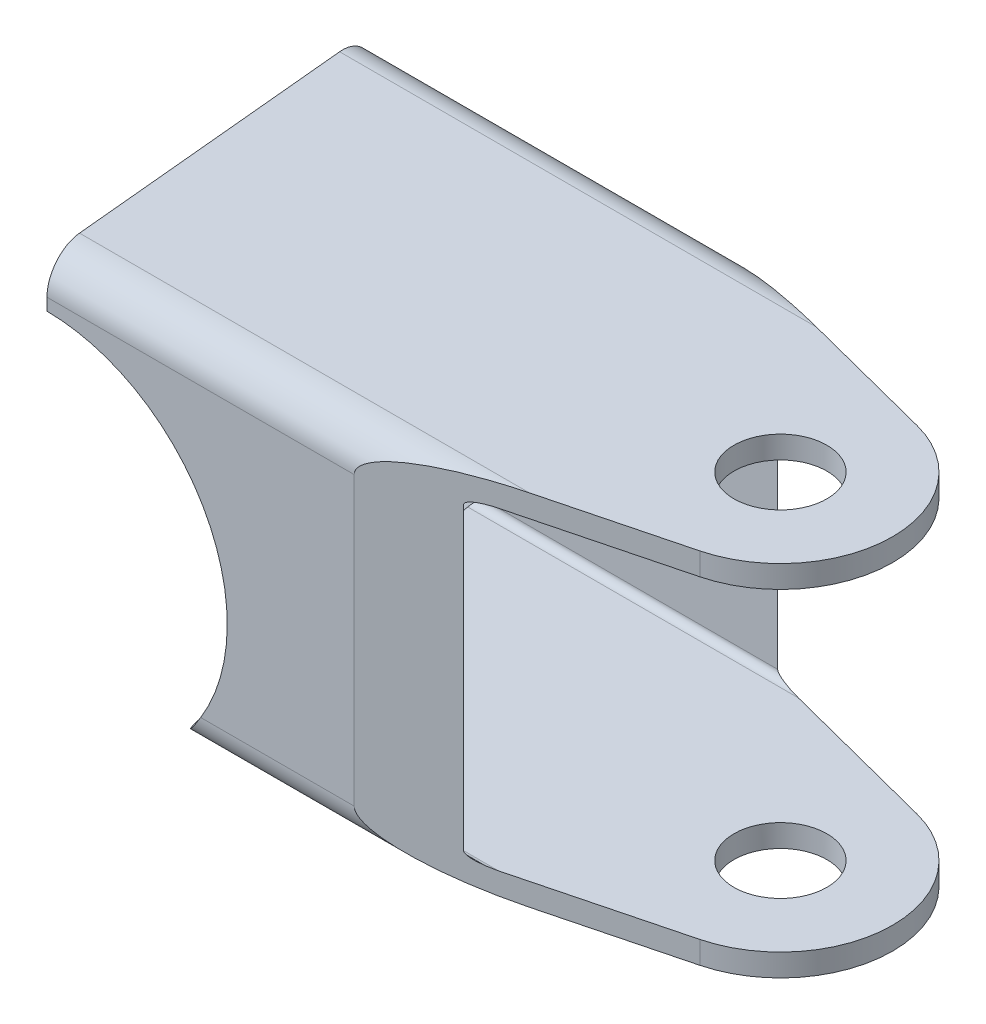
SolidWorks part; units mm, degrees
note: '?' marks a value the reader was unsure of.
material "AISI 4130 Steel, annealed at 865C"
ref_plane "Front Plane" through (0, 0, 0) normal (0, 0, 1) x (1, 0, 0)
ref_plane "Top Plane" through (0, 0, 0) normal (0, 1, 0) x (1, 0, 0)
ref_plane "Right Plane" through (0, 0, 0) normal (1, 0, 0) x (0, 0, -1)
sketch "Sketch1" plane through (0, 0, 0) normal (1, 0, 0) x (0, 0, -1)
  line L1 (-10.16, 12.7) -> (10.16, 12.7)
  line L2 (-12.7, 10.16) -> (-12.7, -10.16)
  line L3 (-10.16, -12.7) -> (10.16, -12.7)
  line L4 (12.7, 10.16) -> (12.7, -10.16)
  arc A0 (-10.16, 12.7) -> (-12.7, 10.16) centre (-10.16, 10.16) ccw
  arc A1 (-10.16, -12.7) -> (-12.7, -10.16) centre (-10.16, -10.16) cw
  arc A2 (10.16, 12.7) -> (12.7, 10.16) centre (10.16, 10.16) cw
  arc A3 (12.7, -10.16) -> (10.16, -12.7) centre (10.16, -10.16) cw
  point P4 (0, -12.7)
  point P7 (0, 0)
  point P15 (12.7, 0)
  dimension "D3" = 2.54
  dimension "D4" = 2.54
  dimension "D5" = 2.54
  dimension "D6" = 2.54
  dimension "D1" = 25.4
  dimension "D2" = 20.32
extrude "Boss-Extrude1" add sketch "Sketch1" along normal blind 25.4 and the other way blind 34.925
sketch "Sketch11" plane through (25.4, 0, 0) normal (1, 0, 0) x (0, 0, -1)
  line L0 (-10.16, -12.7) -> (10.16, -12.7) construction
  line L1 (-10.6045, 11.1125) -> (10.6045, 11.1125)
  line L2 (-11.1125, 10.6045) -> (-11.1125, -10.6045)
  line L3 (-10.6045, -11.1125) -> (10.6045, -11.1125)
  line L4 (11.1125, 10.6045) -> (11.1125, -10.6045)
  line L5 (10.16, 12.7) -> (-10.16, 12.7) construction
  line L6 (12.7, -10.16) -> (12.7, 10.16) construction
  line L7 (-12.7, 10.16) -> (-12.7, -10.16) construction
  arc A0 (10.6045, 11.1125) -> (11.1125, 10.6045) centre (10.6045, 10.6045) cw
  arc A1 (10.6045, -11.1125) -> (11.1125, -10.6045) centre (10.6045, -10.6045) ccw
  arc A2 (-11.1125, -10.6045) -> (-10.6045, -11.1125) centre (-10.6045, -10.6045) ccw
  arc A3 (-10.6045, 11.1125) -> (-11.1125, 10.6045) centre (-10.6045, 10.6045) ccw
  dimension "D1" = 1.5875
  dimension "D2" = 1.5875
  dimension "D3" = 1.5875
  dimension "D4" = 1.5875
  dimension "D5" = 0.508
extrude "Cut-Extrude4" cut sketch "Sketch11" against normal through all
sketch "Sketch12" plane through (0, 12.7, 0) normal (0, 1, 0) x (1, 0, 0)
  line L1 (0, 12.7) -> (50.8, 12.7)
  line L2 (50.8, 12.7) -> (50.8, -12.7)
  line L12 (50.8, -12.7) -> (0, -12.7)
  line L13 (19.4444, -7.6861) -> (0, -12.7)
  line L14 (19.4444, 7.6861) -> (0, 12.7)
  line L15 (-34.925, -12.7) -> (25.4, -12.7) construction
  line L16 (-34.925, 12.7) -> (25.4, 12.7) construction
  line L18 (25.4, 10.16) -> (25.4, -10.16) construction
  arc A1 (19.4444, -7.6861) -> (19.4444, 7.6861) centre (17.4625, 0) ccw
  point P8 (18.1688, 9.2165)
  dimension "D2" = 50.8
  dimension "D1" = 17.4625
extrude "Cut-Extrude5" cut sketch "Sketch12" against normal through all
sketch "Sketch14" plane through (0, 12.7, 0) normal (0, 1, 0) x (1, 0, 0)
  circle A0 centre (17.4625, 0) radius 3.2893
  arc A2 (19.4444, -7.6861) -> (19.4444, 7.6861) centre (17.4625, 0) ccw construction
  point P0 (17.4625, 0)
  point P6 (25.4, 0)
  dimension "D2" = 6.5786
  dimension "D1" = 7.9375
  dimension "D3" = 17.4625
extrude "Cut-Extrude6" cut sketch "Sketch14" against normal through all
ref_axis "Axis1" through (-19.8318, -4.9381, 33.0264) along (-0.0934, 0.0736, -0.9929)?
ref_point "Point2"
ref_plane "Plane1" through (-21.7437, -3.4321, 12.7) normal (-0.0934, 0.0736, -0.9929) x (-0.9956, -0.0069, 0.0931)
sketch "Sketch15" plane through (-21.7437, -3.4321, 12.7) normal (-0.0934, 0.0736, -0.9929) x (-0.9956, -0.0069, 0.0931)
  circle A0 centre (0, 0) radius 12.7
extrude "Cut-Extrude7" cut sketch "Sketch15" against normal through all both and the other way through all
ref_plane "Plane2" through (-22.7371, 0, 2.1386) normal (0.9956, 0, -0.0936) x (-0.0934, 0.0736, -0.9929)
sketch "Sketch17" plane through (-22.7371, 0, 2.1386) normal (0.9956, 0, -0.0936) x (-0.0934, 0.0736, -0.9929)
  line L1 (-29.341, 26.6287) -> (29.7394, 26.6287)
  line L2 (-29.341, 26.6287) -> (-29.341, -28.5202)
  line L3 (-29.341, -28.5202) -> (29.7394, -28.5202)
  line L4 (29.7394, 26.6287) -> (29.7394, -28.5202)
extrude "Cut-Extrude8" cut sketch "Sketch17" against normal through all
